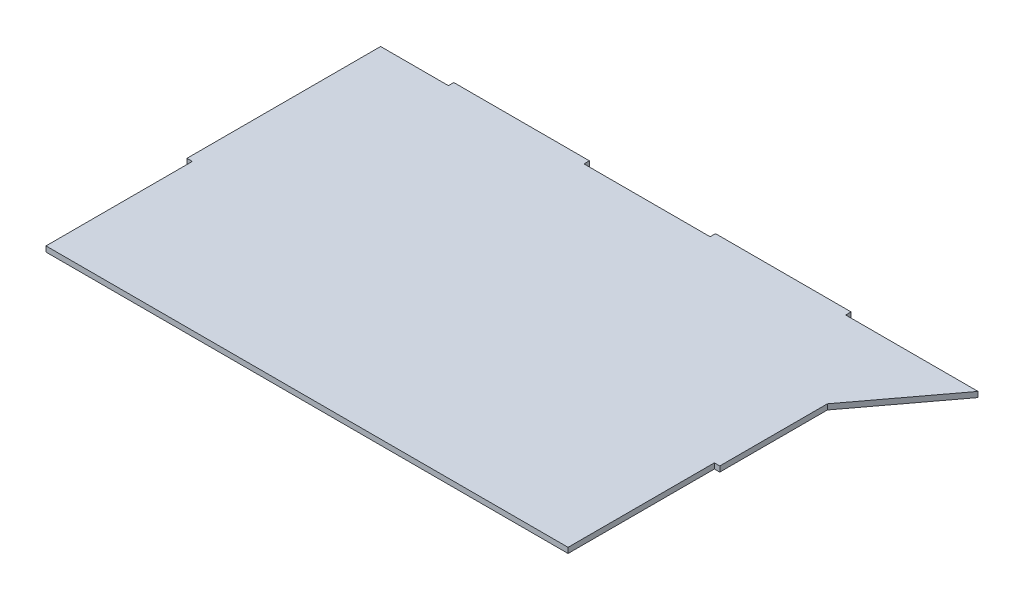
SolidWorks part; units mm, degrees
material "6061-T6 (SS)"
ref_plane "X-Y Datum" through (0, 0, 0) normal (0, 0, 1) x (1, 0, 0)
ref_plane "X-Z Datum" through (0, 0, 0) normal (0, 1, 0) x (1, 0, 0)
ref_plane "Y-Z Datum" through (0, 0, 0) normal (1, 0, 0) x (0, 0, -1)
sketch "Sketch1" plane through (0, 0, 0) normal (0, 0, 1) x (1, 0, 0)
  line L1 (-157.2306, -1.5875) -> (157.2306, -1.5875)
  line L2 (-157.2306, -1.5875) -> (-157.2306, 1.5875)
  line L3 (-157.2306, 1.5875) -> (157.2306, 1.5875)
  line L4 (157.2306, -1.5875) -> (157.2306, 1.5875)
  line L5 (-157.2306, -1.5875) -> (157.2306, 1.5875) construction
  line L6 (-157.2306, 1.5875) -> (157.2306, -1.5875) construction
  point P0 (0, 0)
  dimension "D1" = 314.4612
  dimension "D2" = 3.175
extrude "Boss-Extrude1" add sketch "Sketch1" along normal blind 200.6618
sketch "Sketch3" plane through (0, 0, 0) normal (0, 0, -1) x (-1, 0, 0)
  line L0 (-157.2306, 0) -> (-77.2306, 0) construction
  line L1 (-157.2306, -1.5875) -> (-157.2306, 1.5875) construction
  line L2 (-157.2306, 1.5875) -> (157.2306, 1.5875) construction
  line L3 (-117.2306, -1.5875) -> (-37.2306, -1.5875)
  line L4 (-117.2306, -1.5875) -> (-117.2306, 1.5875)
  line L5 (-117.2306, 1.5875) -> (-37.2306, 1.5875)
  line L6 (-37.2306, -1.5875) -> (-37.2306, 1.5875)
  line L7 (-117.2306, -1.5875) -> (-37.2306, 1.5875) construction
  line L8 (-117.2306, 1.5875) -> (-37.2306, -1.5875) construction
  line L14 (-157.2306, 1.5875) -> (-117.2306, 1.5875)
  line L15 (-157.2306, 1.5875) -> (-157.2306, -1.5875)
  line L16 (-157.2306, -1.5875) -> (-117.2306, -1.5875)
  line L17 (-117.2306, 1.5875) -> (-117.2306, -1.5875)
  line L19 (-37.2306, 1.5875) -> (-37.2306, -1.5875)
  line M3 (-157.2306, -1.5875) -> (157.2306, -1.5875)
  line M5 (157.2306, 1.5875) -> (-157.2306, 1.5875)
  dimension "D1" = 40
  dimension "D2" = 80
sketch "Sketch5" plane through (0, 1.5875, 0) normal (0, 1, 0) x (1, 0, 0)
  line L1 (-157.2306, -200.6618) -> (-154.0556, -200.6618)
  line L3 (-157.2306, -200.6618) -> (-157.2306, -114.3018)
  line L5 (-157.2306, -114.3018) -> (-154.0556, -114.3018)
  line L6 (-154.0556, -200.6618) -> (-154.0556, -114.3018)
  line M11 (-157.2306, 0) -> (-157.2306, -200.6618)
  line M12 (-157.2306, -200.6618) -> (157.2306, -200.6618)
  dimension "D1" = 86.36
  dimension "D2" = 3.175
extrude "Cut-Extrude2" cut sketch "Sketch5" against normal blind 3.175 and the other way through all contours M12 M11 region at (-155.6431, 1.5875, 157.4818)
mirror "Mirror1" about plane through (0, 0, 0) normal (1, 0, 0) of "Cut-Extrude2"
sketch "Sketch6" plane through (0, 1.5875, 0) normal (0, 1, 0) x (1, 0, 0)
  line L6 (-157.2306, -180.3418) -> (-81.0306, -180.3418)
  line L7 (-157.2306, -180.3418) -> (-157.2306, -200.6618)
  line L8 (-157.2306, -200.6618) -> (-81.0306, -200.6618)
  line L9 (-81.0306, -180.3418) -> (-81.0306, -200.6618)
  line L10 (154.0556, -200.6618) -> (-154.0556, -200.6618) construction
  line L11 (-157.2306, -114.3018) -> (-157.2306, 0) construction
  line L13 (154.0556, -200.6618) -> (-81.0306, -200.6618)
  line L14 (154.0556, -200.6618) -> (154.0556, -180.3418)
  line L15 (154.0556, -180.3418) -> (-81.0306, -180.3418)
  line L16 (-81.0306, -200.6618) -> (-81.0306, -180.3418)
  line M18 (-154.0556, -114.3018) -> (-154.0556, -200.6618)
  line M19 (-154.0556, -200.6618) -> (154.0556, -200.6618)
  dimension "D1" = 76.2
  dimension "D2" = 20.32
extrude "Cut-Extrude4" [suppressed] cut sketch "Sketch6" against normal through all contours L9 L6 M18 M19
sketch "Sketch7" [suppressed] plane through (0, 1.5875, 0) normal (0, 1, 0) x (1, 0, 0)
  line L1 (-81.2823, -215.455) -> (155.1963, -215.455)
  line L2 (-81.2823, -215.455) -> (-81.2823, -235.775)
  line L3 (-81.2823, -235.775) -> (155.1963, -235.775)
  line L4 (155.1963, -215.455) -> (155.1963, -235.775)
extrude "Cut-Extrude5" [suppressed] cut sketch "Sketch7" against normal through all
sketch "Sketch8" [suppressed] plane through (0, 1.5875, 0) normal (0, 1, 0) x (1, 0, 0)
  line L0 (155.1963, -235.775) -> (-155.1963, -235.775) construction
  line L1 (157.4823, -215.455) -> (81.2823, -215.455)
  line L2 (157.4823, -215.455) -> (157.4823, -235.775)
  line L3 (157.4823, -235.775) -> (81.2823, -235.775)
  line L4 (81.2823, -215.455) -> (81.2823, -235.775)
  line L5 (157.4823, -117.411) -> (157.4823, -3.175) construction
  dimension "D1" = 20.32
  dimension "D2" = 76.2
extrude "Cut-Extrude6" [suppressed] cut sketch "Sketch8" against normal through all
sketch "Sketch9" [suppressed] plane through (0, 0, 215.455) normal (0, 0, 1) x (1, 0, 0)
  line L4 (155.1963, 1.5875) -> (-155.1963, 1.5875)
  line L5 (-155.1963, 1.5875) -> (-155.1963, -1.5875)
  line L6 (-155.1963, -1.5875) -> (155.1963, -1.5875)
  line L7 (155.1963, -1.5875) -> (155.1963, 1.5875)
  line L8 (155.1963, 1.5875) -> (-155.1963, 1.5875)
  line L9 (-155.1963, 1.5875) -> (-155.1963, -1.5875)
  line L10 (-155.1963, -1.5875) -> (155.1963, -1.5875)
  line L11 (155.1963, -1.5875) -> (155.1963, 1.5875)
  dimension "D1" = 0
extrude "Cut-Extrude7" [suppressed] cut sketch "Sketch9" against normal blind 11.68
extrude "Boss-Extrude2" add sketch "Sketch3" along normal blind 3.175 contours L6 L4 M3 M5 region at (77.2306, 0, 0)
pattern_linear "LPattern2" count 2 spacing 154.43 along (-1, 0, 0) of "Boss-Extrude2"
sketch "Sketch10" plane through (0, -1.5875, 0) normal (0, -1, 0) x (1, 0, 0)
  line L8 (157.2306, 0) -> (195.3306, 0)
  line L9 (195.3306, 0) -> (157.2306, 50.8)
  line L10 (157.2306, 114.3018) -> (157.2306, 0) construction
  line L11 (157.2306, 50.8) -> (157.2306, 0)
  dimension "D1" = 50.8
  dimension "D2" = 38.1
extrude "Boss-Extrude3" add sketch "Sketch10" against normal blind 3.175
sketch "Sketch11" [suppressed] plane through (0, 0, 0) normal (0, 0, -1) x (-1, 0, 0)
  line L1 (37.2652, -1.5875) -> (117.2652, -1.5875)
  line L2 (37.2652, -1.5875) -> (37.2652, 1.5875)
  line L3 (37.2652, 1.5875) -> (117.2652, 1.5875)
  line L4 (117.2652, -1.5875) -> (117.2652, 1.5875)
  line L5 (-117.1668, -1.5875) -> (-37.1668, -1.5875)
  line L6 (-117.1668, -1.5875) -> (-117.1668, 1.5875)
  line L7 (-117.1668, 1.5875) -> (-37.1668, 1.5875)
  line L8 (-37.1668, -1.5875) -> (-37.1668, 1.5875)
extrude "Boss-Extrude4" [suppressed] add sketch "Sketch11" along normal blind 3.175
